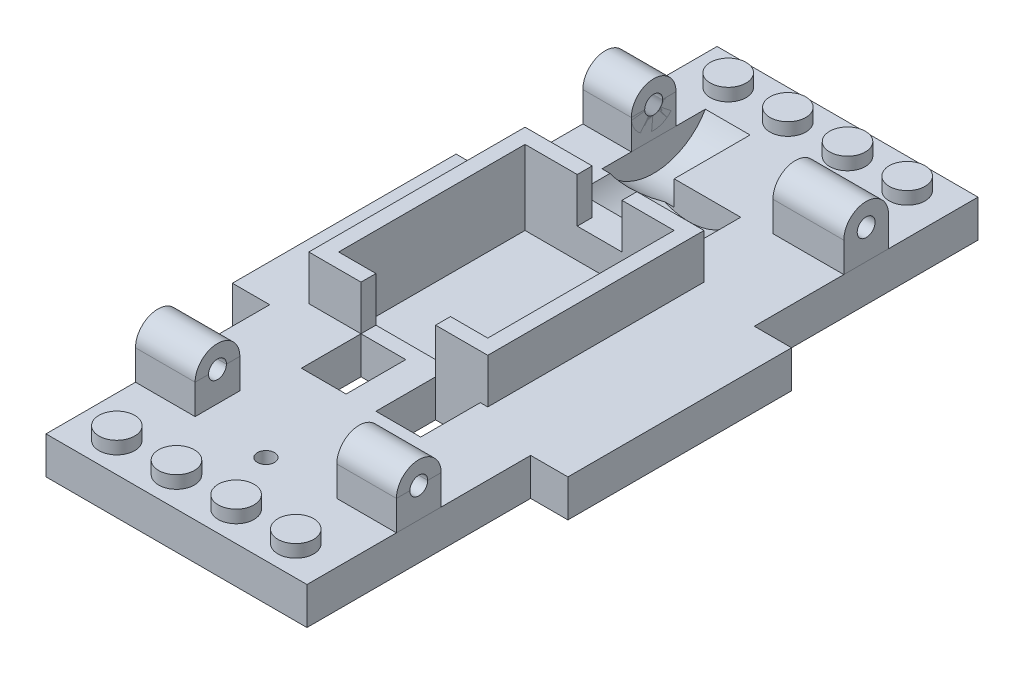
SolidWorks part; units mm, degrees
ref_plane "Front Plane" through (0, 0, 0) normal (0, 0, 1) x (1, 0, 0)
ref_plane "Top Plane" through (0, 0, 0) normal (0, 1, 0) x (1, 0, 0)
ref_plane "Right Plane" through (0, 0, 0) normal (1, 0, 0) x (0, 0, -1)
sketch "Sketch1" plane through (0, 0, 0) normal (0, 1, 0) x (1, 0, 0)
  line L0 (-17.5, -30) -> (17.5, -30) construction
  line L1 (-17.5, 45) -> (17.5, 45)
  line L2 (-17.5, 45) -> (-17.5, -45)
  line L3 (-17.5, -45) -> (17.5, -45)
  line L4 (17.5, 45) -> (17.5, -45)
  line L5 (-17.5, 45) -> (17.5, -45) construction
  line L6 (-17.5, -45) -> (17.5, 45) construction
  line L7 (-17.5, -33) -> (17.5, -33)
  line L8 (-17.5, -33) -> (-17.5, -27)
  line L10 (17.5, -33) -> (17.5, -27)
  line L11 (-17.5, 30) -> (17.5, 30) construction
  line L13 (-17.5, 33) -> (-17.5, 27)
  line L14 (-17.5, 27) -> (17.5, 27)
  line L15 (17.5, 33) -> (17.5, 27)
  line L16 (-17.5, -30) -> (17.5, -30)
  line L17 (-17.5, 30) -> (17.5, 30)
  line L18 (-17.5, -31.2) -> (17.5, -31.2)
  line L19 (0, 45) -> (0, -45) construction
  line L20 (-17.5, 30) -> (-11, 30)
  line L21 (-17.5, 30) -> (-17.5, 27)
  line L22 (-17.5, 27) -> (-11, 27)
  line L23 (-11, 30) -> (-11, 27)
  line L24 (17.5, 27) -> (8, 27)
  line L25 (17.5, 27) -> (17.5, 30)
  line L26 (17.5, 30) -> (8, 30)
  line L27 (8, 27) -> (8, 30)
  line L28 (-11, 28.8) -> (8, 28.8)
  line L29 (-17.5, 30) -> (-11, 30)
  line L30 (-17.5, 30) -> (-17.5, 28.8)
  line L31 (-17.5, 28.8) -> (-11, 28.8)
  line L32 (-11, 30) -> (-11, 28.8)
  line L33 (8, 30) -> (17.5, 30)
  line L34 (8, 30) -> (8, 28.8)
  line L35 (8, 28.8) -> (17.5, 28.8)
  line L36 (17.5, 30) -> (17.5, 28.8)
  line L37 (-17.5, -30) -> (-9.5, -30)
  line L38 (-17.5, -30) -> (-17.5, -33)
  line L39 (-17.5, -33) -> (-9.5, -33)
  line L40 (-9.5, -30) -> (-9.5, -33)
  line L41 (-17.5, -31.2) -> (-9.5, -31.2)
  line L42 (-17.5, -31.2) -> (-17.5, -33)
  line L43 (-17.5, -33) -> (-9.5, -33)
  line L44 (-9.5, -31.2) -> (-9.5, -33)
  line L45 (17.5, -33) -> (9.5, -33)
  line L46 (17.5, -33) -> (17.5, -30)
  line L47 (17.5, -30) -> (9.5, -30)
  line L48 (9.5, -33) -> (9.5, -30)
  line L49 (17.5, -33) -> (9.5, -33)
  line L50 (17.5, -33) -> (17.5, -31.2)
  line L51 (17.5, -31.2) -> (9.5, -31.2)
  line L52 (9.5, -33) -> (9.5, -31.2)
  line L53 (-17.5, 33) -> (17.5, 33)
  line L54 (-17.5, -27) -> (17.5, -27)
  line L55 (-9.5, -33) -> (-9.5, -27)
  line L56 (9.5, -33) -> (9.5, -27)
  line L57 (8, 27) -> (8, 33)
  line L58 (-11, 27) -> (-11, 33)
  line L59 (-17.5, 0) -> (17.5, 0) construction
  line L60 (-9.5, -27) -> (-17.5, -27)
  line L61 (-9.5, -27) -> (-9.5, -33)
  line L62 (-9.5, -33) -> (-17.5, -33)
  line L63 (-17.5, -27) -> (-17.5, -33)
  line L64 (17.5, -27) -> (9.5, -27)
  line L65 (17.5, -27) -> (17.5, -33)
  line L66 (17.5, -33) -> (9.5, -33)
  line L67 (9.5, -27) -> (9.5, -33)
  line L72 (-11, 30) -> (-5, 30)
  line L73 (-11, 30) -> (-11, 38)
  line L74 (-11, 38) -> (-5, 38)
  line L75 (-5, 30) -> (-5, 38)
  line L76 (-5, 30) -> (8, 30)
  line L77 (-5, 30) -> (-5, 34)
  line L78 (-5, 34) -> (8, 34)
  line L79 (8, 30) -> (8, 34)
  line L80 (-17.5, -15) -> (-22.5, -15)
  line L81 (17.5, 15) -> (22.5, 15)
  line L82 (17.5, 15) -> (17.5, -15)
  line L83 (17.5, -15) -> (22.5, -15)
  line L84 (22.5, 15) -> (22.5, -15)
  line L85 (-22.5, 15) -> (-22.5, -15)
  line L86 (-17.5, 15) -> (-22.5, 15)
  line L87 (-17.5, 15) -> (-17.5, -15)
  circle A0 centre (-4, -41) radius 2.4
  circle A1 centre (4, -41) radius 2.4
  circle A2 centre (12, -41) radius 2.4
  circle A3 centre (-12, -41) radius 2.4
  circle A7 centre (12, 41) radius 2.4
  circle A8 centre (4, 41) radius 2.4
  circle A9 centre (-4, 41) radius 2.4
  circle A10 centre (-12, 41) radius 2.4
  point P0 (0, 0)
  point P26 (0, 30)
  point P68 (22.5, 0)
  point P73 (0, 0)
  dimension "D19" = 4.8
  dimension "D1" = 90
  dimension "D2" = 35
  dimension "D3" = 6
  dimension "D4" = 12
  dimension "D5" = 3
  dimension "D6" = 12
  dimension "D7" = 6
  dimension "D8" = 3
  dimension "D9" = 1.2
  dimension "D10" = 11
  dimension "D11" = 8
  dimension "D12" = 1.2
  dimension "D13" = 1.2
  dimension "D14" = 8
  dimension "D15" = 8
  dimension "D16" = 8
  dimension "D17" = 6
  dimension "D18" = 4
  dimension "D20" = 4
  dimension "D21" = 4
  dimension "D25" = 15
  dimension "D26" = 5
  dimension "D22" = 3
  dimension "D23" = 2
  dimension "D24" = 1
extrude "Boss-Extrude1" add sketch "Sketch1" against normal blind 4 contours L35 L27 L14 L25 | L27 L35 L15 L17 | L57 L17 L4 L53 | L31 L21 L14 L23 | L13 L31 L23 L17 | L17 L58 L53 L2 | L65 L64 L67 L66 | L61 L60 L63 L62 region at (-14.25, 0, -31.5) region at (12.75, 0, -31.5) region at (-14.25, 0, -29.4) region at (12.75, 0, -29.4) region at (-14.25, 0, -27.9) region at (12.75, 0, -27.9)
revolve "Revolve1" add sketch "Sketch1<3>" angle 180 about L16 region at (-13.5, 0, 32.1) region at (13.5, 0, 32.1) reverse direction yes
sketch "Sketch1<3>" plane through (0, 0, 0) normal (0, 1, 0) x (1, 0, 0) same geometry as "Sketch1"
revolve "Revolve2" add sketch "Sketch1<5>" angle 360 about L17 region at (-14.25, 0, -27.9) region at (12.75, 0, -27.9)
sketch "Sketch1<5>" plane through (0, 0, 0) normal (0, 1, 0) x (1, 0, 0) same geometry as "Sketch1"
revolve "Cut-Revolve2" cut sketch "Sketch1<6>" angle 360 about L17 region at (-14.25, 0, -29.4) region at (12.75, 0, -29.4) region at (-1.5, 0, -29.4)
sketch "Sketch1<6>" plane through (0, 0, 0) normal (0, 1, 0) x (1, 0, 0) same geometry as "Sketch1"
extrude "Boss-Extrude2" add sketch "Sketch1<7>" against normal blind 5 from offset 4 separate body contours L3 L4 L1 L2 | L80 L85 L86 L87 | L82 L81 L84 L83 offset against normal yes
sketch "Sketch1<7>" plane through (0, 0, 0) normal (0, 1, 0) x (1, 0, 0) same geometry as "Sketch1"
revolve "Cut-Revolve7" cut sketch "Sketch1<9>" angle 360 about L16 region at (-13.5, 0, 30.6) region at (13.5, 0, 30.6)
sketch "Sketch1<9>" plane through (0, 0, 0) normal (0, 1, 0) x (1, 0, 0) same geometry as "Sketch1"
revolve "Cut-Revolve8" cut sketch "Sketch1<10>" angle 360 about L17 region at (-8, 0, -35.5) region at (-8, 0, -31.5) region at (1.5, 0, -31.5) region at (1.5, 0, -33.5)
sketch "Sketch1<10>" plane through (0, 0, 0) normal (0, 1, 0) x (1, 0, 0) same geometry as "Sketch1"
sketch "Sketch4" plane through (0, -4, 0) normal (0, 1, 0) x (1, 0, 0)
  line L0 (-3, -10.25) -> (-3, 39.8847) construction
  line L1 (-13, 14.75) -> (-6, 14.75)
  line L2 (-13, 14.75) -> (-13, -10.25)
  line L3 (-13, -10.25) -> (7, -10.25)
  line L4 (7, 14.75) -> (7, -10.25)
  line L5 (-11, 23.0718) -> (-11, 36.9282) construction
  line L6 (0, 16.75) -> (9, 16.75)
  line L7 (-15, -12.25) -> (9, -12.25)
  line L8 (-15, -12.25) -> (-15, 16.75)
  line L9 (-15, 16.75) -> (-6, 16.75)
  line L10 (9, -12.25) -> (9, 16.75)
  line L11 (-15, -12.25) -> (9, 16.75) construction
  line L12 (-15, 16.75) -> (9, -12.25) construction
  line L14 (-6, 16.75) -> (-6, 14.75)
  line L16 (0, 16.75) -> (0, 14.75)
  line L17 (-6, 14.75) -> (7, 14.75)
  line L18 (2, -10.25) -> (2, -12.25)
  line L19 (-8, -10.25) -> (-8, -12.25)
  point P8 (-3, 2.25)
  point P13 (-11, 30)
  dimension "D1" = 25
  dimension "D2" = 20
  dimension "D3" = 8
  dimension "D4" = 2
  dimension "D5" = 2
  dimension "D6" = 15.25
  dimension "D7" = 2
  dimension "D8" = 7
  dimension "D9" = 7
  dimension "D10" = 5
  dimension "D11" = 5
  dimension "D12" = 12.5
extrude "Cut-Extrude2" cut sketch "Sketch4" against normal blind 4 contours L17 L4 L3 L2 L1
sketch "Sketch9" plane through (0, -9, 0) normal (0, -1, 0) x (1, 0, 0)
  line L0 (0, 45) -> (0, -45) construction
  line L1 (-17.5, 45) -> (17.5, 45) construction
  line L2 (-17.5, -45) -> (17.5, -45) construction
  circle A0 centre (0, 33) radius 1.15
  circle A1 centre (0, -17) radius 1.15
  point P9 (0, 0)
  dimension "D4" = 17
  dimension "D2" = 2.3
  dimension "D3" = 2.3
  dimension "D1" = 12
extrude "Cut-Extrude4" cut sketch "Sketch9" against normal up to next (5 mm away)
sketch "Sketch10" plane through (0, -4, 0) normal (0, 1, 0) x (1, 0, 0)
  line L0 (-15, -12.25) -> (9, -12.25) construction
  line L1 (-8, -12.25) -> (-2, -12.25)
  line L2 (-8, -12.25) -> (-8, -20.25)
  line L3 (-8, -20.25) -> (-2, -20.25)
  line L4 (-2, -12.25) -> (-2, -20.25)
  line L6 (2, -12.25) -> (8, -12.25)
  line L7 (2, -12.25) -> (2, -20.25)
  line L8 (2, -20.25) -> (8, -20.25)
  line L9 (8, -12.25) -> (8, -20.25)
  circle A0 centre (0, -33) radius 1.15 construction
  point P12 (5, -20.25)
  dimension "D1" = 4
  dimension "D2" = 2
  dimension "D3" = 6
  dimension "D4" = 8
  dimension "D5" = 8
  dimension "D6" = 6
extrude "Cut-Extrude5" cut sketch "Sketch10" against normal up to next (5 mm away) contours L2 L1 L4 L3 | L7 L6 L9 L8
extrude "Boss-Extrude3" add sketch "Sketch4<6>" along normal blind 6 contours L19 L3 L2 L1 L14 L9 L8 L7 | L3 L18 L7 L10 L6 L16 L17 L4 region at (-13.3036, -4, -2.25) region at (0.3036, -4, -15.75)
sketch "Sketch4<6>" plane through (0, -4, 0) normal (0, 1, 0) x (1, 0, 0) same geometry as "Sketch4"
ref_plane "Plane1" through (0, 0, 0) normal (0, 1, 0) x (1, 0, 0)
extrude "Boss-Extrude4" add sketch "Sketch1<12>" against normal blind 1.7 from offset 2.3 separate body contours A9 | A8 | A10 | A7 | A2 | A1 | A0 | A3 | A10 region at (-4, 0, 41) region at (4, 0, 41) region at (12, 0, 41) region at (-12, 0, 41) region at (12, 0, -41) region at (4, 0, -41) region at (-4, 0, -41) region at (-12, 0, -41) offset against normal yes
sketch "Sketch1<12>" plane through (0, 0, 0) normal (0, 1, 0) x (1, 0, 0) same geometry as "Sketch1"
sketch "Sketch11" plane through (0, 0, 0) normal (0, 1, 0) x (1, 0, 0)
  line L0 (-6, 16.75) -> (0, 16.75) construction
  line L1 (-3, 16.75) -> (-3, 18.75) construction
  line L2 (-3, -10.25) -> (-3, 39.8847) construction
  line L3 (-3, 18.75) -> (5, 18.75)
  line L4 (5, 18.75) -> (5, 26.75)
  line L5 (5, 26.75) -> (-3, 26.75)
  line L6 (-3, 26.75) -> (-3, 18.75)
  dimension "D1" = 2
  dimension "D2" = 8
  dimension "D3" = 8
revolve "Cut-Revolve9" cut sketch "Sketch11" angle 360 about L6
